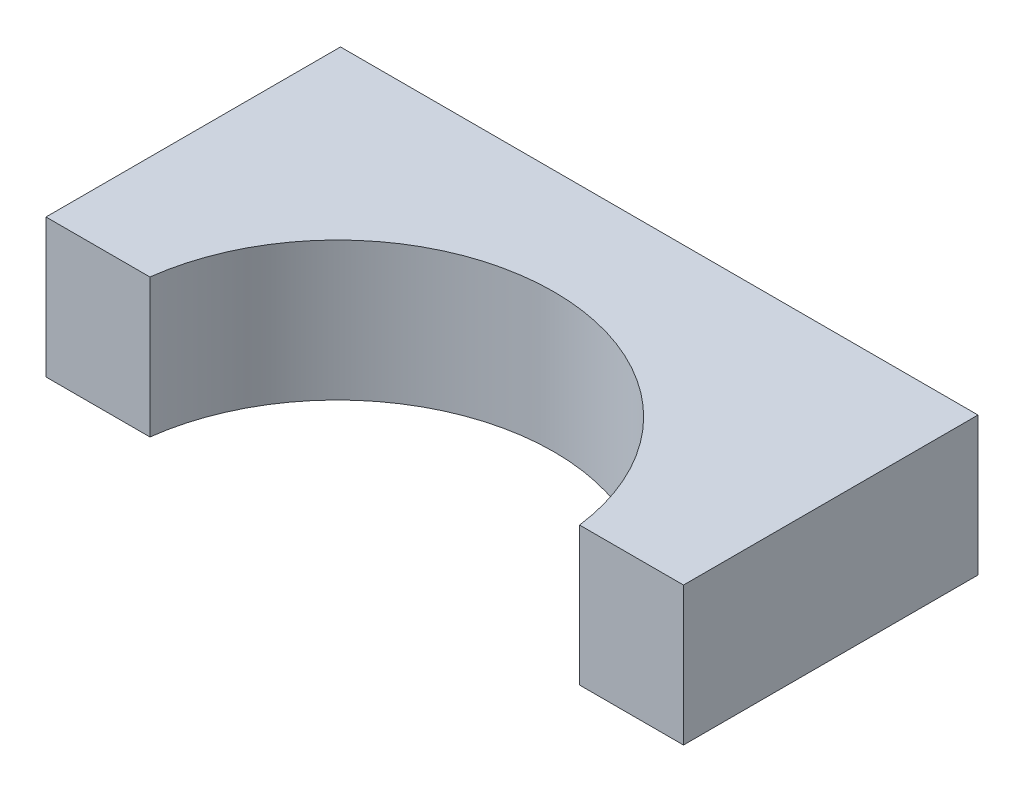
SolidWorks part; units mm, degrees
material "PLA"
ref_plane "Front" through (0, 0, 0) normal (0, 0, 1) x (1, 0, 0)
ref_plane "Top" through (0, 0, 0) normal (0, 1, 0) x (1, 0, 0)
ref_plane "Right" through (0, 0, 0) normal (1, 0, 0) x (0, 0, -1)
sketch "Sketch2" plane through (0, 0, 0) normal (0, 1, 0) x (1, 0, 0)
  line L0 (-14.986, -8.89) -> (-7.366, -8.89)
  line L1 (-14.986, 12.7) -> (31.75, 12.7)
  line L2 (-14.986, 12.7) -> (-14.986, -8.89)
  line L4 (31.75, 12.7) -> (31.75, -8.89)
  line L5 (24.13, -8.89) -> (31.75, -8.89)
  arc A3 (24.13, -8.89) -> (-7.366, -8.89) centre (8.382, -10.894) ccw
  point P0 (0, 0)
  dimension "D5" = 31.75
  dimension "D1" = 46.736
  dimension "D2" = 21.59
  dimension "D3" = 7.62
  dimension "D4" = 7.62
extrude "Boss-Extrude1" add sketch "Sketch2" against normal blind 10.16
sketch "Sketch6" plane through (0, 0, -12.7) normal (0, 0, -1) x (-1, 0, 0)
  line L0 (0, 0) -> (14.986, 0)
  line L1 (14.986, 0) -> (-31.75, 0)
  line L2 (-31.75, 0) -> (-8.382, 0)
  line L3 (-8.382, 0) -> (-8.382, -10.16)
  line L6 (-8.382, -5.08) -> (14.986, -5.08)
  line L7 (14.986, -10.16) -> (14.986, 0) construction
  line L8 (14.986, -5.08) -> (-31.75, -5.08)
  line L9 (-31.75, -10.16) -> (-31.75, 0) construction
  line L10 (-26.924, -5.08) -> (-8.382, -5.08)
  line L11 (-8.382, -5.08) -> (10.16, -5.08)
  circle A0 centre (-26.924, -5.08) radius 1.0033
  circle A1 centre (10.16, -5.08) radius 1.0033
  dimension "D2" = 2.0066
  dimension "D5" = 2.0066
  dimension "D1" = 23.368
  dimension "D3" = 18.542
  dimension "D4" = 18.542
extrude "Cut-Extrude1" cut sketch "Sketch6" against normal blind 4.064 contours L10 A0 L8 | L8 A0 L10 | L8 A1 L11 | L11 A1 L8 region at (-10.16, -4.6542, -12.7) region at (-10.16, -5.5058, -12.7) region at (26.924, -5.5058, -12.7) region at (26.924, -4.6542, -12.7)
